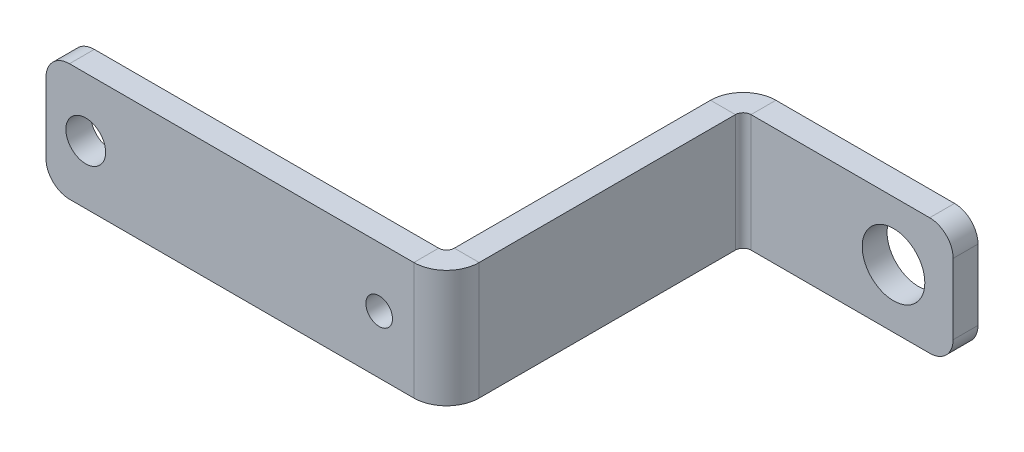
SolidWorks part; units mm, degrees
note: The reader was unsure of these and kept them because the rebuilt part matched: flange length of "Edge-Flange1", "Edge-Flange2".
material "3003-H14"
ref_plane "X-Y Datum" through (0, 0, 0) normal (0, 0, 1) x (1, 0, 0)
ref_plane "X-Z Datum" through (0, 0, 0) normal (0, 1, 0) x (1, 0, 0)
ref_plane "Y-Z Datum" through (0, 0, 0) normal (1, 0, 0) x (0, 0, -1)
sketch "Sketch1" plane through (0, 0, -1943.3334) normal (0, 0, 1) x (1, 0, 0)
  line L7 (74.8293, 321.1281) -> (122.8293, 321.1281)
  line L8 (74.8293, 321.1281) -> (74.8293, 306.1281)
  line L9 (74.8293, 306.1281) -> (122.8293, 306.1281)
  line L10 (122.8293, 321.1281) -> (122.8293, 306.1281)
  point P10 (74.8293, 311.1281)
  dimension "D1" = 15
  dimension "D2" = 48
base flange "Base-Flange1" sketch "Sketch1" thickness 3.175 reverse thickness direction yes parameters "D1"=10
edge flange "Edge-Flange1" sketch "Sketch13" flange angle 90 flange length 37.9125 flange position material outside bend radius 1 thickness 3.175 relief rectangular parameters "D6"=10
bend "EdgeBend3" bend radius 1 bend angle 90 parameters "D5"=1
sketch "Sketch13" plane through (122.8293, 0, -1943.3334) normal (-1, 0, 0) x (0, 1, 0)
  line L0 (321.1281, 0) -> (306.1281, 0) construction
  line L1 (321.1281, 0) -> (306.1281, 0)
  line L2 (321.1281, 0) -> (321.1281, 34.7375)
  line L3 (321.1281, 34.7375) -> (306.1281, 34.7375)
  line L4 (306.1281, 34.7375) -> (306.1281, 0)
edge flange "Edge-Flange2" sketch "Sketch15" flange angle 90 flange length 30 flange position material outside bend radius 1 thickness 3.175 relief rectangular parameters "D6"=10
bend "EdgeBend4" bend radius 1 bend angle 90 parameters "D5"=2
sketch "Sketch15" plane through (126.0043, 0, -1978.0709) normal (0, 0, 1) x (0, -1, 0)
  line L0 (-306.1281, 0) -> (-321.1281, 0) construction
  line L1 (-306.1281, 0) -> (-321.1281, 0)
  line L2 (-306.1281, 0) -> (-306.1281, 26.825)
  line L3 (-306.1281, 26.825) -> (-321.1281, 26.825)
  line L4 (-321.1281, 26.825) -> (-321.1281, 0)
fillet "Fillet1" radius 3 4 edges at (74.8293, 306.1281, -1941.7459) (74.8293, 321.1281, -1941.7459) (152.8293, 306.1281, -1979.6584) (152.8293, 321.1281, -1979.6584)
sketch "Sketch18" plane through (0, 0, -1940.1584) normal (0, 0, 1) x (1, 0, 0)
  line L0 (74.8293, 313.6281) -> (79.9093, 313.6281)
  line L1 (74.8293, 318.1281) -> (74.8293, 309.1281) construction
  circle A0 centre (79.9093, 313.6281) radius 2.54
  dimension "D1" = 5.08
extrude "Cut-Extrude2" cut sketch "Sketch18" against normal through all
sketch "Sketch19" plane through (0, 0, -1978.0709) normal (0, 0, 1) x (1, 0, 0)
  line L0 (152.8293, 313.6281) -> (145.2093, 313.6281) construction
  line L1 (152.8293, 309.1281) -> (152.8293, 318.1281) construction
  circle A0 centre (145.2093, 313.6281) radius 4
  dimension "D1" = 7.62
  dimension "D2" = 8
extrude "Cut-Extrude3" cut sketch "Sketch19" against normal through all
sketch "Sketch20" plane through (0, 0, -1940.1584) normal (0, 0, 1) x (1, 0, 0)
  point P0 (117.4043, 313.5374)
  point P3 (117.4043, 313.5374)
hole_wizard "M3 Clearance Hole1" positions "Sketch20" profile "Sketch21" hole size "M3" standard "ANSI Metric" end condition through all
sketch "Sketch21" plane through (117.4043, 313.5374, -1940.1584) normal (1, 0, 0) x (0, -1, 0)
  line L0 (0, 0) -> (0, 41.0875)
  line L1 (0, 41.0875) -> (1.7, 41.0875)
  line L2 (1.7, 41.0875) -> (1.7, 0)
  line L5 (1.7, 0) -> (0, 0)
  line L11 (0, -6.35) -> (0, 107.95) construction
  dimension "Thru Hole Dia." = 3.4
  dimension "Thru Hole Depth" = 41.0875
sketch "Bend-Lines1" [suppressed] plane through (0, 0, 0) normal (0, 1, 0) x (1, 0, 0)
sketch "Bounding-Box1" [suppressed] plane through (0, 0, 0) normal (0, 1, 0) x (1, 0, 0)
sheet metal parameters "Sheet-Metal1" thickness 3.175 parameters "D1"=10
flat pattern "Flat-Pattern1" [suppressed]
sketch "Bend-Lines2" plane through (0, 0, 0) normal (0, 1, 0) x (1, 0, 0)
sketch3d "Bounding-Box2" [suppressed]
  line L0 (-74.8293, 301.1281, 0) -> (-100.9696, 301.1281, 0) construction
  line L1 (-74.8293, 321.1281, 0) -> (-100.9696, 321.1281, 0) construction
  line L2 (-74.8293, 301.1281, 0) -> (-74.8293, 321.1281, 0) construction
  line L3 (-100.9696, 301.1281, 0) -> (-100.9696, 321.1281, 0) construction
sheet metal parameters "Sheet-Metal2" thickness 3.175 parameters "D1"=10
flat pattern "Flat-Pattern1"
sketch "Bend-Lines2" plane through (0, 0, -1947.5) normal (0, 0, -1) x (-1, 0, 0)
  line L2 (-102.0018, 321.1281) -> (-102.0018, 301.1281) construction
  line L3 (-102.0018, 321.1281) -> (-102.0018, 301.1281) construction
sketch3d "Bounding-Box2" [suppressed]
  line L0 (-74.8293, 301.1281, 0) -> (-139.859, 301.1281, 0) construction
  line L1 (-74.8293, 321.1281, 0) -> (-139.859, 321.1281, 0) construction
  line L2 (-74.8293, 301.1281, 0) -> (-74.8293, 321.1281, 0) construction
  line L3 (-139.859, 301.1281, 0) -> (-139.859, 321.1281, 0) construction
bend of the flat pattern "Flatten-<EdgeBend3>1"
sheet metal parameters "Sheet-Metal3" thickness 3.175 parameters "D1"=10
flat pattern "Flat-Pattern1"
sketch "Bend-Lines2" plane through (0, 0, -1947.295) normal (0, 0, -1) x (-1, 0, 0)
  line L4 (-140.8913, 321.1281) -> (-140.8913, 301.1281) construction
  line L5 (-102.0018, 321.1281) -> (-102.0018, 301.1281) construction
  line L6 (-140.8913, 321.1281) -> (-140.8913, 301.1281) construction
  line L7 (-102.0018, 321.1281) -> (-102.0018, 301.1281) construction
sketch3d "Bounding-Box2" [suppressed]
  line L0 (-74.8293, 301.1281, 0) -> (-188.7485, 301.1281, 0) construction
  line L1 (-74.8293, 321.1281, 0) -> (-188.7485, 321.1281, 0) construction
  line L2 (-74.8293, 301.1281, 0) -> (-74.8293, 321.1281, 0) construction
  line L3 (-188.7485, 301.1281, 0) -> (-188.7485, 321.1281, 0) construction
bend of the flat pattern "Flatten-<EdgeBend3>2"
bend of the flat pattern "Flatten-<EdgeBend4>1"
sheet metal parameters "Sheet-Metal5" thickness 3.175 parameters "D1"=10
flat pattern "Flat-Pattern1" [suppressed]
sketch "Bend-Lines2" plane through (0, 0, -1947.295) normal (0, 0, -1) x (-1, 0, 0)
  line L4 (-140.8913, 321.1281) -> (-140.8913, 301.1281) construction
  line L5 (-102.0018, 321.1281) -> (-102.0018, 301.1281) construction
  line L6 (-140.8913, 321.1281) -> (-140.8913, 301.1281) construction
  line L7 (-102.0018, 321.1281) -> (-102.0018, 301.1281) construction
sketch3d "Bounding-Box2" [suppressed]
  line L0 (-74.8293, 301.1281, 0) -> (-188.7485, 301.1281, 0) construction
  line L1 (-74.8293, 321.1281, 0) -> (-188.7485, 321.1281, 0) construction
  line L2 (-74.8293, 301.1281, 0) -> (-74.8293, 321.1281, 0) construction
  line L3 (-188.7485, 301.1281, 0) -> (-188.7485, 321.1281, 0) construction
bend of the flat pattern "Flatten-<EdgeBend3>2"
bend of the flat pattern "Flatten-<EdgeBend4>1"
sketch "Sketch19-1" [suppressed] plane through (37.7789, 0, -1944.12) normal (0, 0, 1) x (1, 0, 0)
  line L0 (150.9696, 311.1281) -> (145.8896, 311.1281)
  circle A0 centre (145.8896, 311.1281) radius 2.54
  dimension "D1" = 5.08
  dimension "D2" = 5.08
sheet metal parameters "Sheet-Metal6" thickness 3.175 parameters "D1"=10
flat pattern "Flat-Pattern1" [suppressed]
sketch "Bend-Lines2" plane through (0, 0, -1943.3334) normal (0, 0, -1) x (-1, 0, 0)
  line L4 (-160.6634, 321.1281) -> (-160.6634, 301.1281) construction
  line L5 (-123.8615, 321.1281) -> (-123.8615, 301.1281) construction
  line L6 (-160.6634, 321.1281) -> (-160.6634, 301.1281) construction
  line L7 (-123.8615, 321.1281) -> (-123.8615, 301.1281) construction
sketch3d "Bounding-Box2" [suppressed]
  line L0 (-74.8293, 301.1281, 0) -> (-188.5207, 301.1281, 0) construction
  line L1 (-74.8293, 321.1281, 0) -> (-188.5207, 321.1281, 0) construction
  line L2 (-74.8293, 301.1281, 0) -> (-74.8293, 321.1281, 0) construction
  line L3 (-188.5207, 301.1281, 0) -> (-188.5207, 321.1281, 0) construction
bend of the flat pattern "Flatten-<EdgeBend3>2"
bend of the flat pattern "Flatten-<EdgeBend4>1"
sketch "Sketch19-1" plane through (35.6914, 0, -1940.1584) normal (0, 0, 1) x (1, 0, 0)
  line L0 (152.8293, 311.1281) -> (145.2093, 311.1281) construction
  circle A0 centre (145.2093, 311.1281) radius 4
  dimension "D1" = 7.62
  dimension "D2" = 8
sheet metal parameters "Sheet-Metal7" thickness 3.175 parameters "D1"=10
flat pattern "Flat-Pattern1" [suppressed]
sketch "Bend-Lines2" plane through (0, 0, -1943.3334) normal (0, 0, -1) x (-1, 0, 0)
  line L4 (-160.6634, 321.1281) -> (-160.6634, 306.1281) construction
  line L5 (-123.8615, 321.1281) -> (-123.8615, 306.1281) construction
  line L6 (-160.6634, 321.1281) -> (-160.6634, 306.1281) construction
  line L7 (-123.8615, 321.1281) -> (-123.8615, 306.1281) construction
sketch3d "Bounding-Box2" [suppressed]
  line L0 (-74.8293, 306.1281, 0) -> (-188.5207, 306.1281, 0) construction
  line L1 (-74.8293, 321.1281, 0) -> (-188.5207, 321.1281, 0) construction
  line L2 (-74.8293, 306.1281, 0) -> (-74.8293, 321.1281, 0) construction
  line L3 (-188.5207, 306.1281, 0) -> (-188.5207, 321.1281, 0) construction
bend of the flat pattern "Flatten-<EdgeBend3>2"
bend of the flat pattern "Flatten-<EdgeBend4>1"
sketch "Sketch19-1" plane through (35.6914, 0, -1940.1584) normal (0, 0, 1) x (1, 0, 0)
  line L0 (152.8293, 313.6281) -> (145.2093, 313.6281) construction
  circle A0 centre (145.2093, 313.6281) radius 4
  dimension "D1" = 7.62
  dimension "D2" = 8
